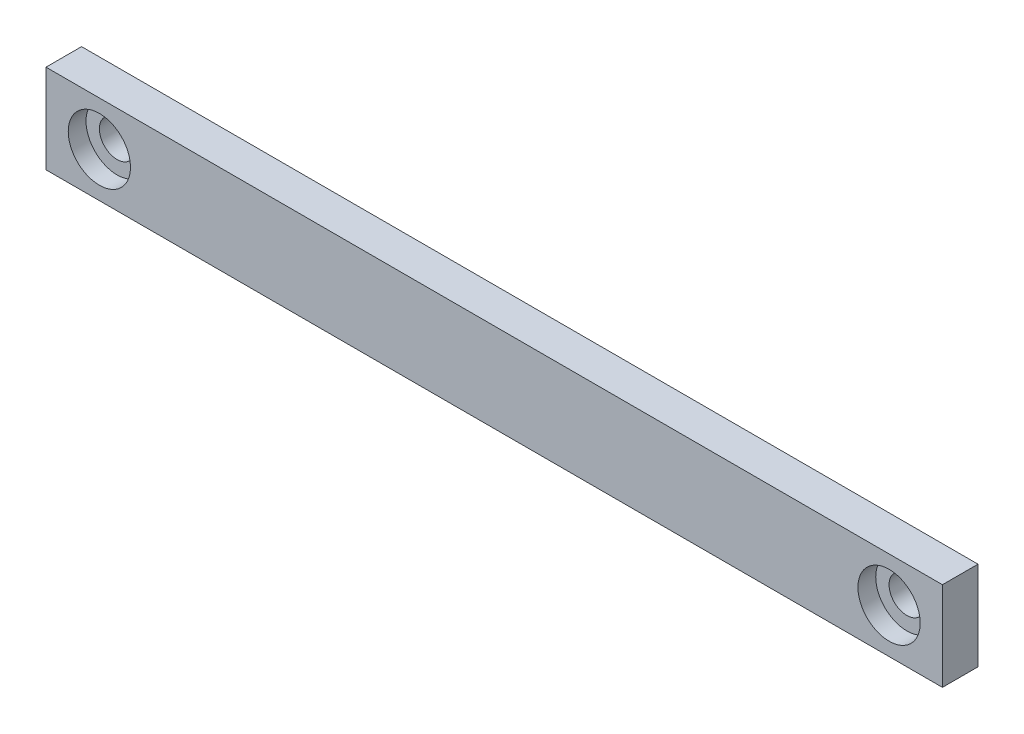
SolidWorks part; units mm, degrees
ref_plane "前视基准面" through (0, 0, 0) normal (0, 0, 1) x (1, 0, 0)
ref_plane "上视基准面" through (0, 0, 0) normal (0, 1, 0) x (1, 0, 0)
ref_plane "右视基准面" through (0, 0, 0) normal (1, 0, 0) x (0, 0, -1)
other "Configuration Table"
sketch "草图1" plane through (0, 0, 0) normal (0, 0, 1) x (1, 0, 0)
  line L6 (0, -5) -> (50.4, -5)
  line L11 (0, -5) -> (0, 0)
  line L12 (0, 0) -> (50.4, 0)
  line L13 (50.4, -5) -> (50.4, 0)
  circle A0 centre (3, -2.5) radius 1.75
  circle A1 centre (3, -2.5) radius 1
  circle A2 centre (47.4, -2.5) radius 1.75
  circle A4 centre (47.4, -2.5) radius 1
  point P8 (47.4, -3)
  point P10 (47.4, -3)
  point P11 (47.384, -2.8)
  dimension "D1" = 5
  dimension "D2" = 3
  dimension "D4" = 2
  dimension "D5" = 3
  dimension "D6" = 44.4
  dimension "D3" = 3.5
  dimension "D7" = 2.5
extrude "凸台-拉伸1" add sketch "草图1" along normal blind 2 contours L12 | L12 L13 L6 L11 | A1 | A4
extrude "切除-拉伸2" cut sketch "草图1<8>" against normal blind 1 from surface contours A0 | A2 starting at face at (25.2, -2.5, 2)
sketch "草图1<8>" plane through (0, 0, 0) normal (0, 0, 1) x (1, 0, 0) same geometry as "草图1"
